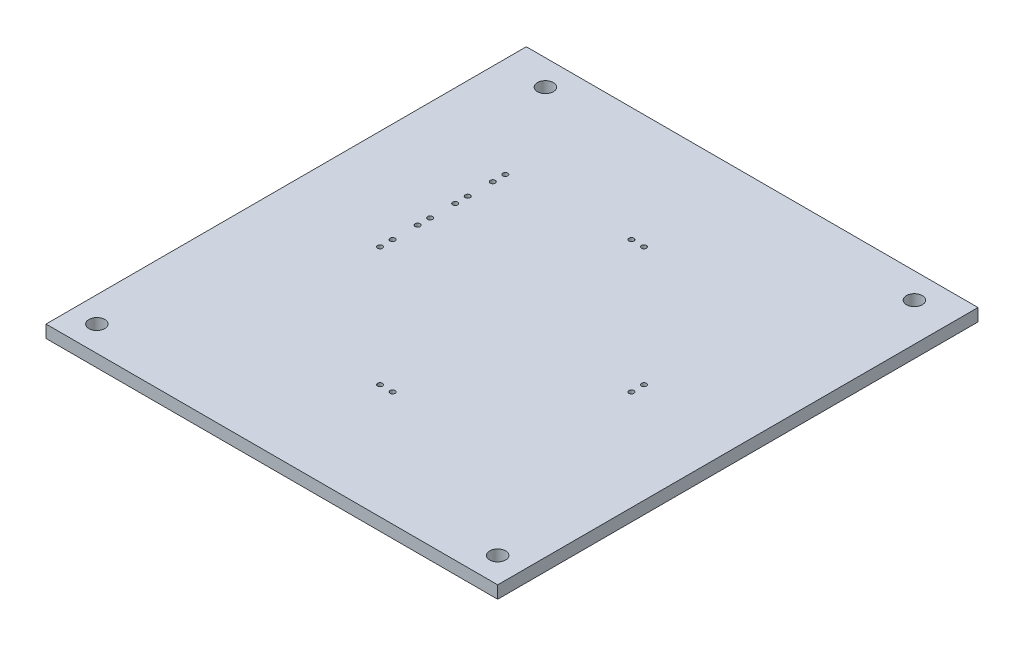
SolidWorks part; units mm, degrees
ref_plane "Front" through (0, 0, 0) normal (0, 0, 1) x (1, 0, 0)
ref_plane "Top" through (0, 0, 0) normal (0, 1, 0) x (1, 0, 0)
ref_plane "Right" through (0, 0, 0) normal (1, 0, 0) x (0, 0, -1)
sketch "Sketch1" plane through (0, 0, 0) normal (0, 1, 0) x (1, 0, 0)
  line L1 (-45.085, -47.9425) -> (45.085, -47.9425)
  line L2 (-45.085, -47.9425) -> (-45.085, 47.9425)
  line L3 (-45.085, 47.9425) -> (45.085, 47.9425)
  line L4 (45.085, -47.9425) -> (45.085, 47.9425)
  line L5 (-45.085, -47.9425) -> (45.085, 47.9425) construction
  line L6 (-45.085, 47.9425) -> (45.085, -47.9425) construction
  point P0 (0, 0)
  dimension "D1" = 95.885
  dimension "D2" = 90.17
extrude "Boss-Extrude1" add sketch "Sketch1" along normal blind 2.5
sketch "Sketch2" plane through (0, 2.5, 0) normal (0, 1, 0) x (1, 0, 0)
  line L0 (-45.085, 47.9425) -> (-45.085, -47.9425) construction
  line L1 (-45.085, -47.9425) -> (45.085, -47.9425) construction
  circle A0 centre (-40.005, -42.8625) radius 1.5875
  circle A1 centre (-36.195, 42.8625) radius 1.5875
  circle A2 centre (37.465, 42.8625) radius 1.5875
  circle A3 centre (40.005, -42.8625) radius 1.5875
  dimension "D1" = 3.175
  dimension "D2" = 5.08
  dimension "D3" = 5.08
  dimension "D4" = 80.01
  dimension "D5" = 85.725
  dimension "D6" = 3.81
  dimension "D7" = 73.66
extrude "Cut-Extrude1" cut sketch "Sketch2" against normal blind 2.5
sketch "Sketch3" plane through (0, 2.5, 0) normal (0, 1, 0) x (1, 0, 0)
  line L0 (-45.085, 47.9425) -> (-45.085, -47.9425) construction
  circle A0 centre (-25.085, 1.25) radius 0.5
  circle A1 centre (-25.085, -1.25) radius 0.5
  dimension "D1" = 1
  dimension "D2" = 1.25
  dimension "D3" = 2.5
  dimension "D4" = 20
extrude "Cut-Extrude2" cut sketch "Sketch3" against normal blind 10
ref_axis "Axis1" through (0, 50, 0) along (0, -1, 0)
pattern_circular "CirPattern1" count 4 over 360 about axis through (0, 50, 0) along (0, -1, 0) of "Cut-Extrude2"
pattern_linear "LPattern1" count 4 spacing 7.5 along (0, 0, -1) of "Cut-Extrude2"
